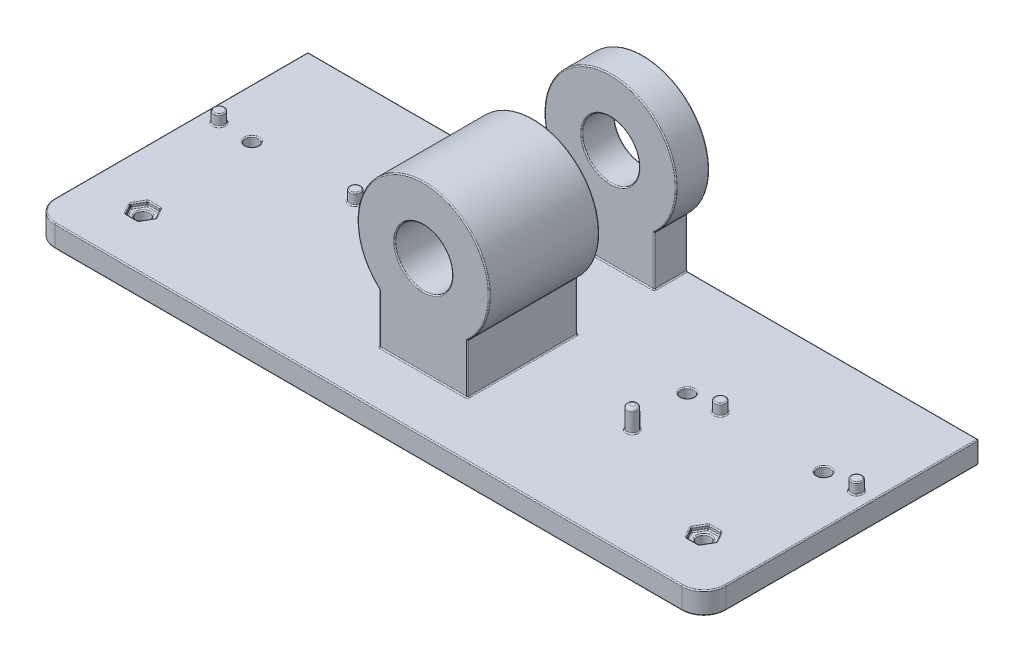
SolidWorks part; units mm, degrees
ref_plane "Front Plane" through (0, 0, 0) normal (0, 0, 1) x (1, 0, 0)
ref_plane "Top Plane" through (0, 0, 0) normal (0, 1, 0) x (1, 0, 0)
ref_plane "Right Plane" through (0, 0, 0) normal (1, 0, 0) x (0, 0, -1)
sketch "Sketch1" plane through (0, 0, 0) normal (0, 1, 0) x (1, 0, 0)
  line L0 (152.5, 125) -> (152.5, 0) construction
  line L1 (0, 0) -> (305, 0)
  line L2 (0, 0) -> (0, 125)
  line L3 (0, 125) -> (305, 125)
  line L4 (305, 0) -> (305, 125)
  line L5 (25, 100) -> (280, 100) construction
  line L6 (280, 25) -> (280, 100) construction
  line L7 (25, 25) -> (280, 25) construction
  line L8 (25, 25) -> (25, 100) construction
  line L9 (152.5, 62.5) -> (25, 62.5) construction
  line L10 (30.7735, 100) -> (27.8868, 105) construction
  line L11 (27.8868, 105) -> (22.1132, 105) construction
  line L12 (22.1132, 105) -> (19.2265, 100) construction
  line L13 (19.2265, 100) -> (22.1132, 95) construction
  line L14 (22.1132, 95) -> (27.8868, 95) construction
  line L15 (27.8868, 95) -> (30.7735, 100) construction
  line L16 (27.8868, 30) -> (30.7735, 25) construction
  line L17 (22.1132, 30) -> (27.8868, 30) construction
  line L18 (19.2265, 25) -> (22.1132, 30) construction
  line L19 (22.1132, 20) -> (19.2265, 25) construction
  line L20 (27.8868, 20) -> (22.1132, 20) construction
  line L21 (30.7735, 25) -> (27.8868, 20) construction
  line L22 (282.8868, 30) -> (277.1132, 30) construction
  line L23 (285.7735, 25) -> (282.8868, 30) construction
  line L24 (282.8868, 20) -> (285.7735, 25) construction
  line L25 (277.1132, 20) -> (282.8868, 20) construction
  line L26 (274.2265, 25) -> (277.1132, 20) construction
  line L27 (277.1132, 30) -> (274.2265, 25) construction
  line L28 (277.1132, 95) -> (274.2265, 100) construction
  line L29 (282.8868, 95) -> (277.1132, 95) construction
  line L30 (285.7735, 100) -> (282.8868, 95) construction
  line L31 (282.8868, 105) -> (285.7735, 100) construction
  line L32 (277.1132, 105) -> (282.8868, 105) construction
  line L33 (274.2265, 100) -> (277.1132, 105) construction
  line L34 (172.5, 75) -> (172.5, 125) construction
  line L35 (132.5, 0) -> (172.5, 0) construction
  line L36 (132.5, 0) -> (132.5, 125) construction
  line L37 (132.5, 125) -> (172.5, 125) construction
  line L38 (172.5, 0) -> (172.5, 125) construction
  line L39 (132.5, 75) -> (172.5, 75) construction
  line L40 (132.5, 75) -> (132.5, 25) construction
  line L41 (132.5, 25) -> (172.5, 25) construction
  line L42 (172.5, 75) -> (172.5, 25) construction
  line L51 (0, 84.5) -> (15, 69.5) construction
  line L52 (132.5, 75) -> (117.5, 70) construction
  line L53 (117.5, 70) -> (117.5, 95) construction
  line L54 (0, 125) -> (108, 125) construction
  line L55 (0, 125) -> (0, 84.5) construction
  line L56 (0, 84.5) -> (108, 84.5) construction
  line L57 (108, 125) -> (108, 84.5) construction
  line L58 (15, 69.5) -> (15, 84.5) construction
  line L59 (30, 84.5) -> (0, 84.5) construction
  line L60 (30, 84.5) -> (30, 69.5) construction
  line L61 (30, 69.5) -> (0, 69.5) construction
  line L62 (0, 84.5) -> (0, 69.5) construction
  line L63 (92, 84.5) -> (92, 69.5) construction
  line L64 (62, 0) -> (62, 125) construction
  circle A1 centre (25, 100) radius 5 construction
  circle A3 centre (280, 25) radius 3
  circle A4 centre (25, 25) radius 3
  circle A8 centre (117.5, 70) radius 3
  circle A9 centre (117.5, 95) radius 3
  circle A10 centre (7.5, 77) radius 3 construction
  circle A11 centre (22.5, 77) radius 3
  circle A12 centre (69.5, 77) radius 3 construction
  circle A13 centre (84.5, 77) radius 3
  circle A14 centre (220.5, 77) radius 3
  circle A15 centre (235.5, 77) radius 3 construction
  circle A16 centre (282.5, 77) radius 3
  circle A17 centre (297.5, 77) radius 3 construction
  point P82 (0, 0)
  point P83 (117.5, 62.5)
  point P84 (0, 0)
  point P85 (117.5, 67.735)
  dimension "D3" = 6
  dimension "D1" = 305
  dimension "D2" = 125
  dimension "D5" = 10
  dimension "D6" = 40
  dimension "D8" = 50
  dimension "D12" = 15
  dimension "D7" = 40.5
  dimension "D9" = 108
  dimension "D10" = 15
  dimension "D11" = 30
  dimension "D15" = 62
  dimension "D16" = 5
  dimension "D17" = 25
  dimension "D4" = 25
  dimension "D13" = 2
  dimension "D14" = 2
extrude "Boss-Extrude1" add sketch "Sketch1" along normal blind 10
sketch "Sketch6" plane through (0, 10, 0) normal (0, 1, 0) x (1, 0, 0)
  line L0 (152.5, 125) -> (152.5, 0) construction
  line L7 (305, 125) -> (0, 125) construction
  line L8 (0, 0) -> (305, 0) construction
  line L9 (152.5, 62.5) -> (0, 62.5) construction
  line L10 (0, 125) -> (0, 0) construction
  line L29 (27.8868, 30) -> (30.7735, 25)
  line L30 (274.2265, 25) -> (277.1132, 20)
  line L31 (277.1132, 20) -> (282.8868, 20)
  line L32 (282.8868, 20) -> (285.7735, 25)
  line L33 (285.7735, 25) -> (282.8868, 30)
  line L34 (282.8868, 30) -> (277.1132, 30)
  line L35 (277.1132, 30) -> (274.2265, 25)
  line L36 (22.1132, 30) -> (27.8868, 30)
  line L37 (19.2265, 25) -> (22.1132, 30)
  line L38 (22.1132, 20) -> (19.2265, 25)
  line L39 (27.8868, 20) -> (22.1132, 20)
  line L40 (30.7735, 25) -> (27.8868, 20)
  circle A0 centre (280, 25) radius 5 construction
  dimension "D1" = 10
extrude "Cut-Extrude1" cut sketch "Sketch6" against normal blind 2
sketch "Sketch7" plane through (0, 10, 0) normal (0, 1, 0) x (1, 0, 0)
  line L0 (0, 0) -> (305, 0) construction
  line L1 (132.5, 25) -> (172.5, 25)
  line L2 (132.5, 25) -> (132.5, 75)
  line L3 (132.5, 75) -> (172.5, 75)
  line L4 (172.5, 25) -> (172.5, 75)
  line L5 (152.5, 0) -> (152.5, 125) construction
  line L6 (305, 125) -> (0, 125) construction
  line L7 (172.5, 75) -> (172.5, 125) construction
  line L18 (132.5, 110) -> (172.5, 110)
  line L19 (132.5, 110) -> (132.5, 125)
  line L20 (132.5, 125) -> (172.5, 125)
  line L21 (172.5, 110) -> (172.5, 125)
  point P11 (152.5, 75)
  point P20 (152.5, 110)
  dimension "D1" = 40
  dimension "D2" = 50
  dimension "D4" = 15
extrude "Boss-Extrude2" add sketch "Sketch7" along normal blind 22.6393
sketch "Sketch11" plane through (0, 0, -25) normal (0, 0, 1) x (1, 0, 0)
  circle A0 centre (152.5, 55) radius 30
  circle A1 centre (152.5, 55) radius 13
  dimension "D1" = 60
  dimension "D2" = 26
extrude "Boss-Extrude3" add sketch "Sketch11" against normal up to surface (100 mm away) up to face at (152.5, 13.1598, -125)
ref_plane "Plane1" through (0, 0, -62.5) normal (0, 0, 1) x (1, 0, 0)
sketch "Sketch12" plane through (305, 0, 0) normal (1, 0, 0) x (0, 0, -1)
  line L0 (125, 85) -> (25, 85) construction
  line L1 (75, 10) -> (110, 10)
  line L2 (75, 10) -> (75, 85)
  line L3 (75, 85) -> (110, 85)
  line L4 (110, 10) -> (110, 85)
  line L6 (110, 32.6393) -> (110, 10) construction
extrude "Cut-Extrude2" cut sketch "Sketch12" against normal through all
sketch "Sketch13" plane through (0, 10, 0) normal (0, 1, 0) x (1, 0, 0)
  line L0 (222.5, 50) -> (172.5, 50) construction
  line L1 (172.5, 25) -> (172.5, 75) construction
  circle A1 centre (222.5, 50) radius 2.4
  dimension "D1" = 4.8
  dimension "D2" = 50
extrude "Boss-Extrude4" add sketch "Sketch13" along normal blind 10
fillet "Fillet1" radius 1.3 1 edges at (222.5, 20, -47.6)
sketch "Sketch15" plane through (0, 10, 0) normal (0, 1, 0) x (1, 0, 0)
  line L0 (69.5, 77) -> (7.5, 77) construction
  line L1 (38.5, 77) -> (38.5, 84.5) construction
  line L2 (0, 84.5) -> (108, 84.5) construction
  line L3 (152.5, 125) -> (152.5, 0) construction
  circle A1 centre (69.5, 77) radius 2.5
  circle A2 centre (7.5, 77) radius 2.5
  circle A3 centre (7.5, 77) radius 2.5
  circle A4 centre (235.5, 77) radius 2.5
  circle A5 centre (297.5, 77) radius 2.5
  dimension "D1" = 0.5
extrude "Boss-Extrude5" add sketch "Sketch15" along normal blind 5
chamfer "Chamfer1" distance 3.3 angle 45 6 edges at (282.5, 0, -74) (220.5, 0, -74) (84.5, 0, -80) (22.5, 0, -80) (117.5, 0, -67) (117.5, 0, -92)
fillet "Fillet2" radius 0.5 93 edges at (25, 0, -28) (19.2265, 9, -25) (22.1132, 9, -20) (27.8868, 9, -30) (22.1132, 9, -30) (27.8868, 9, -20) (30.7735, 9, -25) (29.3301, 8, -27.5) (29.3301, 8, -22.5) (25, 8, -20) (20.6699, 8, -22.5) (20.6699, 8, -27.5) (25, 8, -30) (25, 8, -28) (280, 0, -22) (277.1132, 9, -30) (274.2265, 9, -25) (285.7735, 9, -25) (282.8868, 9, -30) (277.1132, 9, -20) (282.8868, 9, -20) (280, 8, -30) (284.3301, 8, -27.5) (284.3301, 8, -22.5) (280, 8, -20) (275.6699, 8, -22.5) (275.6699, 8, -27.5) (280, 8, -22) (235.5, 15, -74.5) (297.5, 15, -79.5) (69.5, 15, -79.5) (7.5, 15, -74.5) (117.5, 10, -67) (280, 10, -20) (284.3301, 10, -22.5) (284.3301, 10, -27.5) (280, 10, -30) (275.6699, 10, -27.5) (275.6699, 10, -22.5) (20.6699, 10, -22.5) (25, 10, -20) (29.3301, 10, -22.5) (29.3301, 10, -27.5) (25, 10, -30) (20.6699, 10, -27.5) (117.5, 10, -92) (305, 10, -62.5) (152.5, 10, 0) (0, 10, -62.5) (22.5, 10, -80) (84.5, 10, -80) (220.5, 10, -74) (282.5, 10, -74) (222.5, 10, -52.4) (7.5, 10, -79.5) (69.5, 10, -79.5) (235.5, 10, -79.5) (297.5, 10, -79.5) (165.5, 55, -25) (152.5, 10, -25) (152.5, 85, -25) (132.5, 32.6393, -50) (132.5, 21.3197, -25) (132.5, 10, -50) (165.5, 55, -75) (152.5, 10, -75) (152.5, 85, -75) (132.5, 21.3197, -75) (172.5, 21.3197, -25) (172.5, 32.6393, -50) (172.5, 21.3197, -75) (172.5, 10, -50) (172.5, 32.6393, -117.5) (172.5, 10, -117.5) (132.5, 32.6393, -117.5) (132.5, 10, -117.5) (165.5, 55, -125) (66.25, 10, -125) (0, 5, -125) (152.5, 0, -125) (305, 5, -125) (238.75, 10, -125) (172.5, 21.3197, -125) (152.5, 85, -125) (132.5, 21.3197, -125) (139.5, 55, -110) (152.5, 10, -110) (132.5, 21.3197, -110) (152.5, 85, -110) (172.5, 21.3197, -110) (305, 0, -62.5) (152.5, 0, 0) (0, 0, -62.5)
fillet "Fillet3" radius 10 6 edges at (0.1464, 0.1464, -0.1464) (0.1464, 9.8536, -0.1464) (304.8536, 0.1464, -0.1464) (304.8536, 9.8536, -0.1464) (305, 5, 0) (0, 5, 0)
equation "\"joint_width\"=4"
equation "\"D2@Sketch7\"=5"
equation "\"short_base_length\"=12.5"
equation "\"D2@Sketch1\"=\"short_base_length\""
equation "\"outer_diam_main_joint\"=6"
equation "\"D1@Sketch11\"=\"outer_diam_main_joint\""
equation "\"D1@Sketch7\"=\"outer_diam_main_joint\"-2"
equation "\"D1@Boss-Extrude2\"=(\"outer_diam_main_joint\"/2)+1.5cm-sqr((\"outer_diam_main_joint\"/2)^2-((\"outer_diam_main_joint\"-2)/2)^2)"
equation "\"D6@Sketch1\"=\"outer_diam_main_joint\"-2"
equation "\"pulleyside\"=1.5"
